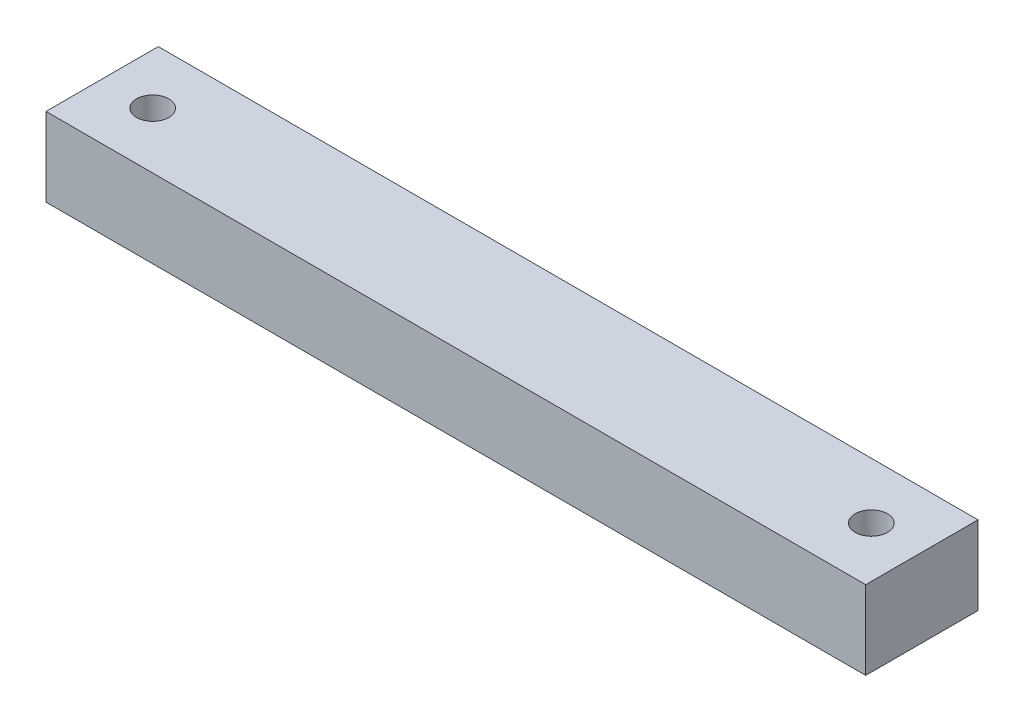
SolidWorks part; units mm, degrees
ref_plane "Front Plane" through (0, 0, 0) normal (0, 0, 1) x (1, 0, 0)
ref_plane "Top Plane" through (0, 0, 0) normal (0, 1, 0) x (1, 0, 0)
ref_plane "Right Plane" through (0, 0, 0) normal (1, 0, 0) x (0, 0, -1)
sketch "Sketch1" plane through (0, 0, 0) normal (0, 1, 0) x (1, 0, 0)
  line L1 (0, 0) -> (92.71, 0)
  line L2 (0, 0) -> (0, -12.7)
  line L3 (0, -12.7) -> (92.71, -12.7)
  line L4 (92.71, 0) -> (92.71, -12.7)
  point P9 (46.355, 0)
  point P10 (0, -6.35)
  dimension "D1" = 92.71
  dimension "D2" = 12.7
extrude "Boss-Extrude1" add sketch "Sketch1" along normal blind 8.89
hole_wizard "#27 (0.144) Diameter Hole1" positions "Sketch3" profile "Sketch2" hole size "#27" standard "ANSI Inch" end condition through all
sketch "Sketch3" plane through (0, 8.89, 0) normal (0, 1, 0) x (1, 0, 0)
  line L0 (92.71, 0) -> (0, 0) construction
  line L1 (0, 0) -> (0, -12.7) construction
  point P0 (5.715, -6.35)
  point P2 (86.995, -6.35)
  point P5 (46.355, 0)
  point P8 (0, -6.35)
  dimension "D1" = 81.28
  dimension "D2" = 40.64
  dimension "D3" = 0
  dimension "D4" = 0
sketch "Sketch2" plane through (5.715, 8.89, 6.35) normal (1, 0, 0) x (0, 0, 1)
  line L0 (0, 0) -> (0, 8.89)
  line L1 (0, 8.89) -> (1.8288, 8.89)
  line L2 (1.8288, 8.89) -> (1.8288, 0)
  line L5 (1.8288, 0) -> (0, 0)
  line L11 (0, -6.35) -> (0, 107.95) construction
  dimension "Thru Hole Dia." = 3.6576
  dimension "Thru Hole Depth" = 8.89
